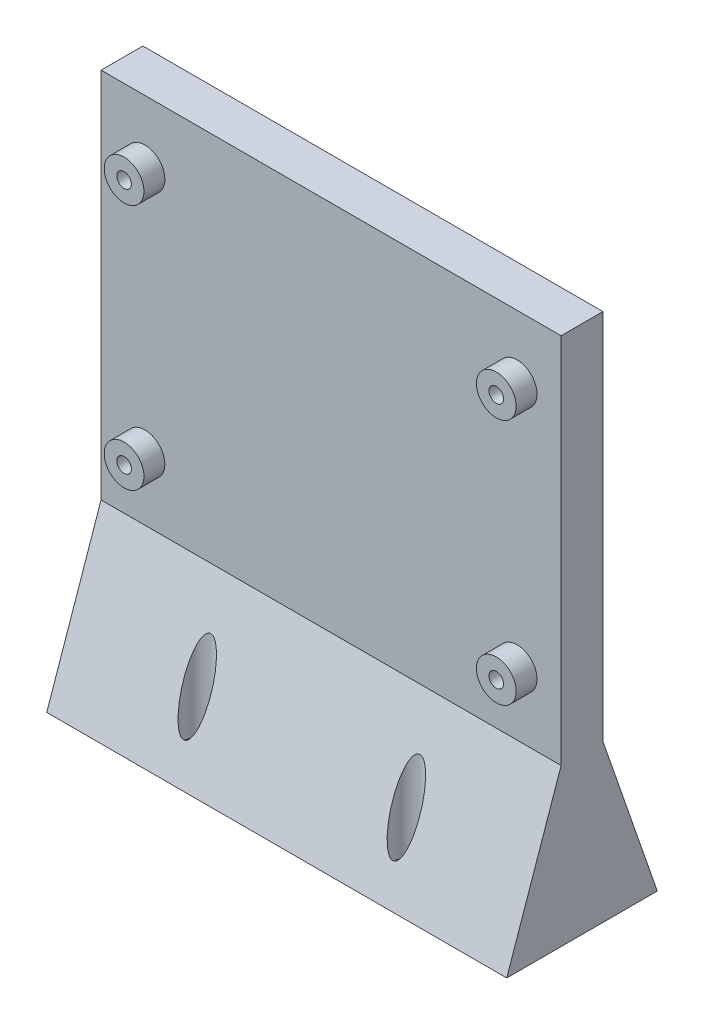
SolidWorks part; units mm, degrees
note: The reader was unsure of these and kept them because the rebuilt part matched: shared geometry of "Sketch1<3>".
ref_plane "Front Plane" through (0, 0, 0) normal (0, 0, 1) x (1, 0, 0)
ref_plane "Top Plane" through (0, 0, 0) normal (0, 1, 0) x (1, 0, 0)
ref_plane "Right Plane" through (0, 0, 0) normal (1, 0, 0) x (0, 0, -1)
sketch "Sketch1" plane through (0, 0, 0) normal (0, 0, 1) x (1, 0, 0)
  line L0 (-55, -82) -> (55, -82) construction
  line L1 (-44.5, -29.5) -> (44.5, -29.5) construction
  line L2 (-44.5, -29.5) -> (-44.5, 29.5) construction
  line L3 (-44.5, 29.5) -> (44.5, 29.5) construction
  line L4 (44.5, -29.5) -> (44.5, 29.5) construction
  line L5 (-44.5, -29.5) -> (44.5, 29.5) construction
  line L6 (-44.5, 29.5) -> (44.5, -29.5) construction
  line L7 (-55, 44.5) -> (55, 44.5)
  line L8 (-55, 44.5) -> (-55, -44.5)
  line L9 (-55, -44.5) -> (55, -44.5)
  line L10 (55, 44.5) -> (55, -44.5)
  circle A0 centre (-44.5, 29.5) radius 1.75
  circle A1 centre (44.5, 29.5) radius 1.75
  circle A2 centre (44.5, -29.5) radius 1.75
  circle A3 centre (-44.5, -29.5) radius 1.75
  circle A4 centre (-44.5, 29.5) radius 4.75
  circle A5 centre (-44.5, -29.5) radius 4.75
  circle A6 centre (44.5, -29.5) radius 4.75
  circle A7 centre (44.5, 29.5) radius 4.75
  point P0 (0, 0)
  point P14 (0, 44.5)
  dimension "D3" = 3.5
  dimension "D5" = 3
  dimension "D1" = 89
  dimension "D2" = 59
  dimension "D4" = 110
  dimension "D6" = 15
  dimension "D7" = 52.5
  dimension "D8" = 15
extrude "Boss-Extrude1" add sketch "Sketch1" along normal blind 10 contours L10 L7 L8 L9 A7 A6 A5 A4
extrude "Boss-Extrude2" add sketch "Sketch1<3>" along normal offset from surface (15 mm away) 5 contours A4 A0 | A7 A1 | A6 A2 | A5 A3 up to face at (49.25, 29.5, 10) offset beyond the face yes
sketch "Sketch1<3>" plane through (0, 0, 0) normal (0, 0, 1) x (1, 0, 0) same geometry as "Sketch1"
ref_plane "Plane1" through (0, -82, 0) normal (0, 1, 0) x (1, 0, 0)
sketch "Sketch2" plane through (0, -82, 0) normal (0, 1, 0) x (1, 0, 0)
  line L0 (55, -10) -> (55, 0) construction
  line L1 (-55, -23) -> (55, -23)
  line L2 (-55, -23) -> (-55, 13)
  line L3 (-55, 13) -> (55, 13)
  line L4 (55, -23) -> (55, 13)
  line L5 (-55, -23) -> (55, 13) construction
  line L6 (-55, 13) -> (55, -23) construction
  line L7 (-55, -10) -> (-55, 0) construction
  point P0 (0, -5)
  point P7 (55, -5)
  dimension "D1" = 36
loft "Loft1" add profiles "Sketch2" section face at (0, -44.5, 5) section "Sketch2"
ref_plane "Plane2" through (0, -44.5, 0) normal (0, 1, 0) x (1, 0, 0)
hole_wizard "CBORE for M3 SHCS1" positions "Sketch3" profile "Sketch5" counterbore size "M3" standard "ANSI Metric" end condition through all
sketch "Sketch3" plane through (0, -44.5, 0) normal (0, 1, 0) x (1, 0, 0)
  line L1 (-25, 7) -> (25, 7) construction
  line L2 (-25, 7) -> (-25, -17) construction
  line L3 (-25, -17) -> (25, -17) construction
  line L4 (25, 7) -> (25, -17) construction
  line L5 (-25, 7) -> (25, -17) construction
  line L7 (55, 13) -> (-55, -23) construction
  point P0 (-25, 7)
  point P2 (25, 7)
  point P4 (25, -17)
  point P6 (-25, -17)
  point P149 (0, -5)
  point P150 (0, -5)
  dimension "D1" = 50
  dimension "D2" = 24
sketch "Sketch5" plane through (-25, -44.5, -7) normal (1, 0, 0) x (0, 0, 1)
  line L0 (0, 0) -> (0, 37.5001)
  line L1 (0, 37.5001) -> (1.7, 37.5001)
  line L3 (1.7, 37.5001) -> (1.7, 33)
  line L4 (1.7, 33) -> (3.25, 33)
  line L5 (3.25, 33) -> (3.25, 0)
  line L7 (3.25, 0) -> (0, 0)
  line L11 (0, -6.35) -> (0, 107.95) construction
  dimension "Thru Hole Dia." = 3.4
  dimension "Thru Hole Depth" = 37.5001
  dimension "C'Bore Dia." = 6.5
  dimension "C'Bore Depth" = 33
